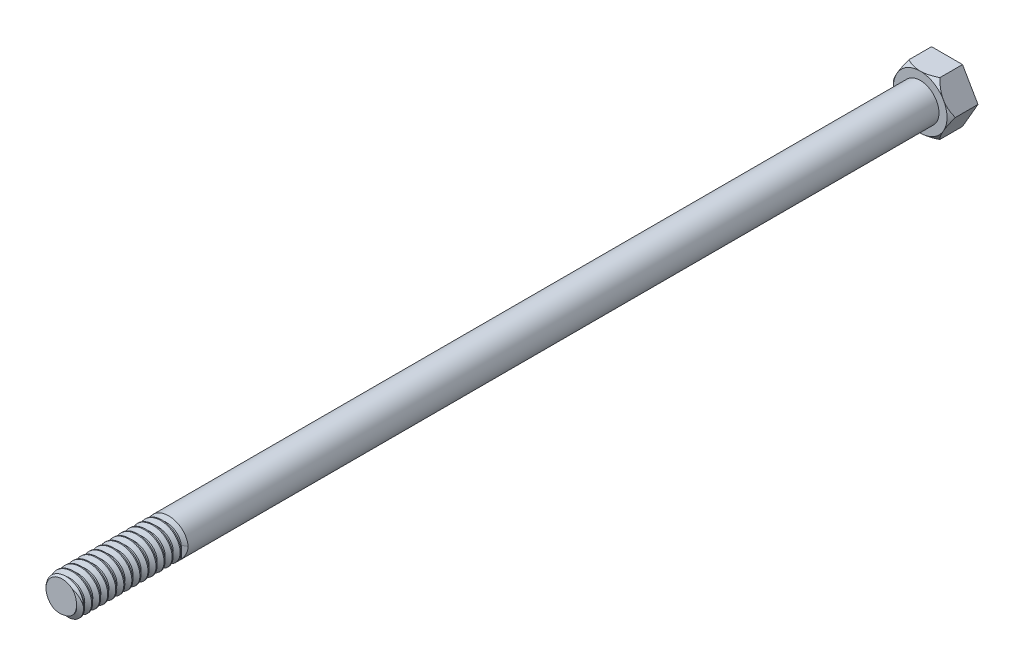
SolidWorks part; units mm, degrees
ref_plane "Front Plane" through (0, 0, 0) normal (0, 0, 1) x (1, 0, 0)
ref_plane "Top Plane" through (0, 0, 0) normal (0, 1, 0) x (1, 0, 0)
ref_plane "Right Plane" through (0, 0, 0) normal (1, 0, 0) x (0, 0, -1)
sketch "Sketch2" plane through (0, 0, 0) normal (0, 0, 1) x (1, 0, 0)
  line L1 (-2.8868, 5) -> (-5.7735, 0)
  line L2 (-5.7735, 0) -> (-2.8868, -5)
  line L3 (-2.8868, -5) -> (2.8868, -5)
  line L4 (2.8868, -5) -> (5.7735, 0)
  line L5 (5.7735, 0) -> (2.8868, 5)
  line L6 (2.8868, 5) -> (-2.8868, 5)
  circle A0 centre (0, 0) radius 5 construction
  dimension "D1" = 10
extrude "Boss-Extrude1" add sketch "Sketch2" along normal mid plane 5
sketch "Sketch3" plane through (0, 0, 2.5) normal (0, 0, 1) x (1, 0, 0)
  line L0 (-2.8868, 5) -> (-5.7735, 0) construction
  circle A0 centre (0, 0) radius 5
extrude "Cut-Extrude1" cut sketch "Sketch3" against normal through all draft 45 flip side to cut
sketch "Sketch4" plane through (0, 0, 2.5) normal (0, 0, 1) x (1, 0, 0)
  circle A0 centre (0, 0) radius 3.5
  dimension "D1" = 7
extrude "Boss-Extrude2" add sketch "Sketch4" along normal blind 160
chamfer "Chamfer1" distance 0.5 angle 45 1 edges at (3.5, 0, 162.5)
thread "Thread1" pitch 1.5 method cut profile "Thread Profile1" start angle 0, offset 140, length 0, pitch 1.5, diameter 7
ref_plane "Plane1" through (3.5, 0, 142.5) normal (0, -1, 0) x (1, 0, 0)
sketch "Thread Profile1" plane through (3.5, 0, 142.5) normal (0, -1, 0) x (1, 0, 0)
  line L0 (0, 0) -> (0, 1.5) construction
  line L11 (0, 0) -> (0, 1.3125)
  line L12 (0, 1.3125) -> (-0.8119, 0.8437)
  line L13 (-0.8119, 0.8437) -> (-0.8119, 0.4687)
  line L15 (-0.8119, 0.4687) -> (0, 0)
  line L17 (-0.8119, 0.6562) -> (0, 0.6562) construction
  point P2 (0, 0)
  dimension "Pitch" = 1.5
  dimension "Profile_Angle" = 60
  dimension "Profile_Land" = 0.375
  dimension "Profile_Height" = 0.8119
sketch "Sketch12" plane through (0, 0, 0) normal (0, 1, 0) x (1, 0, 0)
  line L4 (3.5, -142.5) -> (2.6881, -142.9687)
  line L5 (2.6881, -142.9687) -> (2.6881, -143.3437)
  line L6 (2.6881, -143.3437) -> (3.5, -143.8125)
  line L7 (3.5, -143.8125) -> (3.5, -142.5)
  line L8 (3.5, -142.5) -> (2.6881, -142.9687)
  line L9 (2.6881, -142.9687) -> (2.6881, -143.3437)
  line L10 (2.6881, -143.3437) -> (3.5, -143.8125)
  line L11 (3.5, -143.8125) -> (3.5, -142.5)
  dimension "D1" = 0
extrude "Cut-Extrude2" cut sketch "Sketch12" against normal through all
sketch "Sketch13" plane through (0, 0, -2.5) normal (0, 0, -1) x (-1, 0, 0)
  line L1 (2.5177, 1.4123) -> (0.0357, 2.8865)
  line L2 (0.0357, 2.8865) -> (-2.482, 1.4742)
  line L3 (-2.482, 1.4742) -> (-2.5177, -1.4123)
  line L4 (-2.5177, -1.4123) -> (-0.0357, -2.8865)
  line L5 (-0.0357, -2.8865) -> (2.482, -1.4742)
  line L6 (2.482, -1.4742) -> (2.5177, 1.4123)
  circle A1 centre (0, 0) radius 2.5 construction
  dimension "D1" = 5
extrude "Cut-Extrude4" cut sketch "Sketch13" against normal blind 2.5
